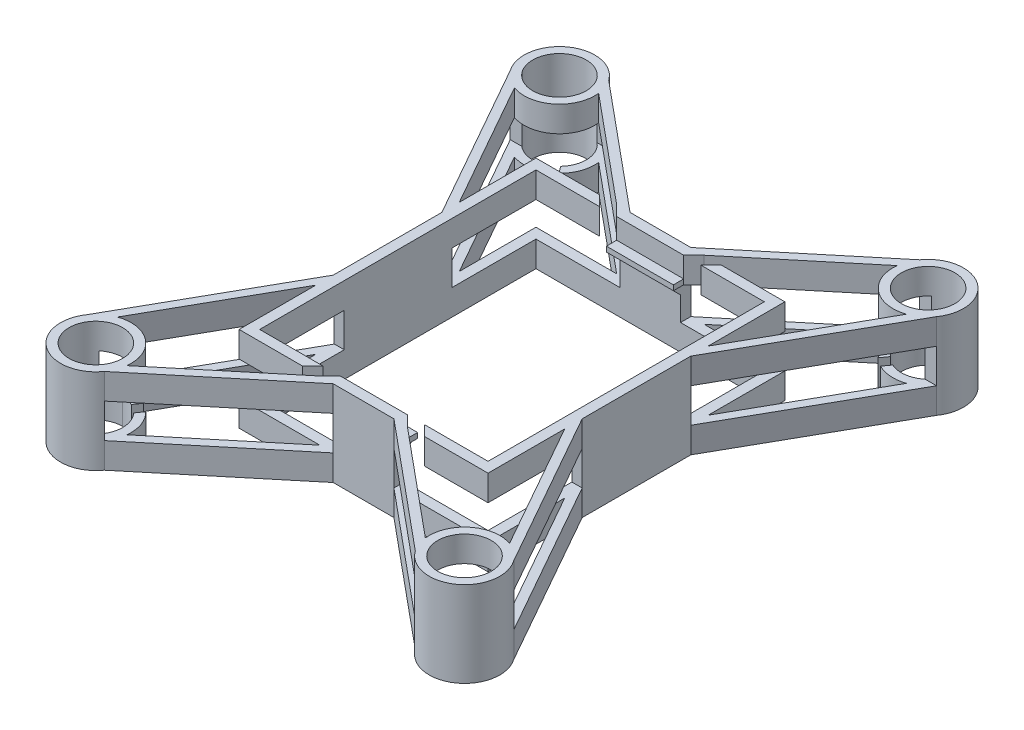
SolidWorks part; units mm, degrees
ref_plane "Front Plane" through (0, 0, 0) normal (0, 0, 1) x (1, 0, 0)
ref_plane "Top Plane" through (0, 0, 0) normal (0, 1, 0) x (1, 0, 0)
ref_plane "Right Plane" through (0, 0, 0) normal (1, 0, 0) x (0, 0, -1)
sketch "Sketch2" plane through (0, 0, 0) normal (0, 1, 0) x (1, 0, 0)
  line L0 (-24.0396, 23.0747) -> (-14.6061, 23.0747)
  line L1 (-22.8396, 21.8747) -> (3.8604, 21.8747)
  line L2 (-22.8396, 21.8747) -> (-22.8396, -10.4253)
  line L3 (-22.8396, -10.4253) -> (3.8604, -10.4253)
  line L4 (3.8604, 21.8747) -> (3.8604, -10.4253)
  line L5 (5.0604, 23.0747) -> (5.0604, 14.1087)
  line L6 (-24.0396, -11.6253) -> (-14.6061, -11.6253)
  line L7 (-24.0396, 23.0747) -> (-24.0396, 14.1087)
  line L8 (-32.4061, 28.9285) -> (-24.0396, 14.1087)
  line L9 (-26.9395, 33.3027) -> (-14.6061, 23.0747)
  line L10 (-34.4055, 30.4359) -> (-24.0396, 12.0747)
  line L11 (-27.6714, 35.2089) -> (-13.0396, 23.0747)
  line L12 (-33.5347, 30.9275) -> (-23.1688, 12.5663) construction
  line L13 (-28.3098, 34.4391) -> (-13.6779, 22.3049) construction
  line L14 (-24.0396, 12.0747) -> (-24.0396, -0.6253)
  line L15 (-24.0396, 23.0747) -> (-24.0396, -11.6253) construction
  line L16 (-13.0396, 23.0747) -> (-5.9396, 23.0747)
  line L17 (-24.0396, 23.0747) -> (5.0604, 23.0747) construction
  line L18 (-9.4896, 43.1002) -> (-9.4896, -24.274) construction
  line L19 (-35.8782, 5.7247) -> (17.7365, 5.7247) construction
  line L20 (8.6923, 35.2089) -> (-5.9396, 23.0747)
  line L21 (7.9603, 33.3027) -> (-4.373, 23.0747)
  line L22 (15.4263, 30.4359) -> (5.0604, 12.0747)
  line L23 (13.427, 28.9285) -> (5.0604, 14.1087)
  line L24 (-27.6714, -23.7596) -> (-13.0396, -11.6253)
  line L25 (-26.9395, -21.8534) -> (-14.6061, -11.6253)
  line L26 (-34.4055, -18.9866) -> (-24.0396, -0.6253)
  line L27 (-32.4061, -17.4792) -> (-24.0396, -2.6594)
  line L28 (8.6923, -23.7596) -> (-5.9396, -11.6253)
  line L29 (7.9603, -21.8534) -> (-4.373, -11.6253)
  line L30 (13.427, -17.4792) -> (5.0604, -2.6594)
  line L31 (15.4263, -18.9866) -> (5.0604, -0.6253)
  line L32 (-4.373, 23.0747) -> (5.0604, 23.0747)
  line L33 (5.0604, 12.0747) -> (5.0604, -0.6253)
  line L34 (5.0604, 23.0747) -> (5.0604, -11.6253) construction
  line L35 (5.0604, -2.6594) -> (5.0604, -11.6253)
  line L36 (-4.373, -11.6253) -> (5.0604, -11.6253)
  line L37 (-24.0396, -11.6253) -> (5.0604, -11.6253) construction
  line L38 (-13.0396, -11.6253) -> (-5.9396, -11.6253)
  line L39 (-24.0396, -2.6594) -> (-24.0396, -11.6253)
  circle A0 centre (-31.0384, 32.8223) radius 3.127
  arc A1 (-27.6714, 35.2089) -> (-34.4055, 30.4359) centre (-31.0384, 32.8223) ccw
  circle A2 centre (-31.0384, 32.8223) radius 4.127 construction
  arc A3 (-32.4061, 28.9285) -> (-26.9395, 33.3027) centre (-31.0384, 32.8223) ccw
  arc A4 (13.427, 28.9285) -> (7.9603, 33.3027) centre (12.0592, 32.8223) cw
  arc A5 (8.6923, 35.2089) -> (15.4263, 30.4359) centre (12.0592, 32.8223) cw
  circle A6 centre (12.0592, 32.8223) radius 3.127
  arc A7 (-32.4061, -17.4792) -> (-26.9395, -21.8534) centre (-31.0384, -21.373) cw
  arc A8 (-27.6714, -23.7596) -> (-34.4055, -18.9866) centre (-31.0384, -21.373) cw
  circle A9 centre (-31.0384, -21.373) radius 3.127
  circle A10 centre (12.0592, -21.373) radius 3.127
  arc A11 (8.6923, -23.7596) -> (15.4263, -18.9866) centre (12.0592, -21.373) ccw
  arc A12 (13.427, -17.4792) -> (7.9603, -21.8534) centre (12.0592, -21.373) ccw
  point P8 (-13.0396, 23.0747)
  point P9 (-24.0396, 12.0747)
  point P17 (-31.0384, 32.8223)
  point P42 (12.0592, 32.8223)
  point P54 (-31.0384, -21.373)
  point P65 (12.0592, -21.373)
  dimension "D6" = 6.254
  dimension "D11" = 6.254
  dimension "D1" = 26.7
  dimension "D2" = 32.3
  dimension "D4" = 11
  dimension "D5" = 11
  dimension "D8" = 1
  dimension "D9" = 1
  dimension "D10" = 12
  dimension "D3" = 1.2
  dimension "D7" = 1
extrude "Boss-Extrude1" add sketch "Sketch2" along normal blind 10
sketch "Sketch4" plane through (0, 0, 0) normal (1, 0, 0) x (0, 0, -1)
  line L1 (-18.9866, 10) -> (-18.9866, 0) construction
  line L2 (30.4359, 10) -> (30.4359, 0) construction
  line L5 (-18.9866, 5) -> (-18.9866, 7)
  line L6 (-18.9866, 7) -> (30.4359, 7)
  line L7 (30.4359, 5) -> (30.4359, 7)
  line L9 (-18.9866, 5) -> (-18.9866, 3)
  line L10 (-18.9866, 3) -> (30.4359, 3)
  line L11 (30.4359, 5) -> (30.4359, 3)
  dimension "D1" = 2
  dimension "D2" = 2
extrude "Cut-Extrude1" cut sketch "Sketch4" against normal through all both and the other way through all
sketch "Sketch5" plane through (0, 0, 0) normal (0, 0, 1) x (1, 0, 0)
  line L1 (-27.6714, 10) -> (-27.6714, 0) construction
  line L2 (8.6923, 10) -> (8.6923, 0) construction
  line L5 (-27.6714, 5) -> (-27.6714, 7)
  line L6 (-27.6714, 7) -> (8.6923, 7)
  line L7 (8.6923, 5) -> (8.6923, 7)
  line L9 (8.6923, 5) -> (8.6923, 3)
  line L10 (8.6923, 3) -> (-27.6714, 3)
  line L11 (-27.6714, 5) -> (-27.6714, 3)
extrude "Cut-Extrude2" cut sketch "Sketch5" against normal through all both and the other way through all
sketch "Sketch6" plane through (-27.6714, 0, 0) normal (1, 0, 0) x (0, 0, -1)
  line L0 (30.4359, 3) -> (30.4359, 7) construction
  line L1 (30.4359, 7) -> (35.2089, 7)
  line L2 (30.4359, 7) -> (30.4359, 3)
  line L3 (30.4359, 3) -> (35.2089, 3)
  line L4 (35.2089, 7) -> (35.2089, 3)
  line L5 (35.2089, 7) -> (30.4359, 7) construction
extrude "Cut-Extrude3" cut sketch "Sketch6" against normal up to surface (1.3465 mm away) up to face at (-31.0384, 5, -30.0656)
sketch "Sketch7" plane through (-27.6714, 0, 0) normal (1, 0, 0) x (0, 0, -1)
  line L1 (-23.7596, 7) -> (-18.9866, 7)
  line L2 (-23.7596, 7) -> (-23.7596, 3)
  line L3 (-23.7596, 3) -> (-18.9866, 3)
  line L4 (-18.9866, 7) -> (-18.9866, 3)
extrude "Cut-Extrude4" cut sketch "Sketch7" against normal up to surface (1.3462 mm away) up to face at (-31.0384, 5, 18.6163)
sketch "Sketch8" plane through (8.6923, 0, 0) normal (-1, 0, 0) x (0, 0, 1)
  line L0 (-35.2089, 3) -> (-30.4359, 3) construction
  line L1 (-35.2089, 7) -> (-30.4359, 7)
  line L2 (-35.2089, 7) -> (-35.2089, 3)
  line L3 (-35.2089, 3) -> (-30.4359, 3)
  line L4 (-30.4359, 7) -> (-30.4359, 3)
  line L5 (-30.4359, 7) -> (-30.4359, 3) construction
extrude "Cut-Extrude5" cut sketch "Sketch8" against normal up to surface (1.3462 mm away) up to face at (12.0592, 5, -30.0656)
sketch "Sketch9" plane through (8.6923, 0, 0) normal (-1, 0, 0) x (0, 0, 1)
  line L1 (18.9866, 7) -> (23.7596, 7)
  line L2 (18.9866, 7) -> (18.9866, 3)
  line L3 (18.9866, 3) -> (23.7596, 3)
  line L4 (23.7596, 7) -> (23.7596, 3)
extrude "Cut-Extrude6" cut sketch "Sketch9" against normal up to surface (1.3465 mm away) up to face at (12.0592, 5, 18.6163)
sketch "Sketch10" plane through (0, 3, 0) normal (0, 1, 0) x (1, 0, 0)
  line L0 (-22.8396, 21.8747) -> (-22.8396, -10.4253) construction
  line L1 (-24.0396, 12.0747) -> (-22.8396, 12.0747)
  line L2 (-24.0396, 12.0747) -> (-24.0396, -0.536)
  line L3 (-24.0396, -0.536) -> (-22.8396, -0.536)
  line L4 (-22.8396, 12.0747) -> (-22.8396, -0.536)
  line L5 (3.8604, 21.8747) -> (-22.8396, 21.8747) construction
  line L6 (-13.0396, 23.0747) -> (-5.9396, 23.0747)
  line L7 (-13.0396, 23.0747) -> (-13.0396, 21.8747)
  line L8 (-13.0396, 21.8747) -> (-5.9396, 21.8747)
  line L9 (-5.9396, 23.0747) -> (-5.9396, 21.8747)
  line L10 (-22.8396, -10.4253) -> (3.8604, -10.4253) construction
  line L15 (3.8604, -10.4253) -> (3.8604, 21.8747) construction
  line L16 (5.0604, 12.0747) -> (3.8604, 12.0747)
  line L17 (5.0604, 12.0747) -> (5.0604, -0.6253)
  line L18 (5.0604, -0.6253) -> (3.8604, -0.6253)
  line L19 (3.8604, 12.0747) -> (3.8604, -0.6253)
  line L20 (-13.0396, -11.6253) -> (-5.9396, -11.6253)
  line L21 (-13.0396, -11.6253) -> (-13.0396, -10.4253)
  line L22 (-13.0396, -10.4253) -> (-5.9396, -10.4253)
  line L23 (-5.9396, -11.6253) -> (-5.9396, -10.4253)
extrude "Boss-Extrude2" add sketch "Sketch10" along normal up to surface (4 mm away) up to face at (-9.4896, 7, -5.7247)
sketch "Sketch11" plane through (0, 0, 0) normal (0, -1, 0) x (1, 0, 0)
  line L0 (-24.0396, 11.6253) -> (-31.0384, 21.373) construction
  line L1 (-29.0577, 19.6641) -> (-30.0523, 18.9499)
  line L2 (-30.0523, 18.9499) -> (-28.7834, 17.1827)
  line L3 (-28.7834, 17.1827) -> (-27.7888, 17.8968)
  line L4 (-27.7888, 17.8968) -> (-29.0577, 19.6641)
  line L5 (-9.4896, 17.1827) -> (-9.4896, -28.9277) construction
  line L6 (-86.1455, -5.7247) -> (24.0687, -5.7247)
  line L7 (9.8043, 17.1827) -> (8.8097, 17.8968)
  line L8 (11.0732, 18.9499) -> (9.8043, 17.1827)
  line L9 (10.0786, 19.6641) -> (11.0732, 18.9499)
  line L10 (8.8097, 17.8968) -> (10.0786, 19.6641)
  line L11 (-28.7834, -28.632) -> (-27.7888, -29.3461)
  line L12 (-30.0523, -30.3992) -> (-28.7834, -28.632)
  line L13 (-29.0577, -31.1134) -> (-30.0523, -30.3992)
  line L14 (-27.7888, -29.3461) -> (-29.0577, -31.1134)
  line L15 (11.0732, -30.3992) -> (9.8043, -28.632)
  line L16 (10.0786, -31.1134) -> (11.0732, -30.3992)
  line L17 (8.8097, -29.3461) -> (10.0786, -31.1134)
  line L18 (9.8043, -28.632) -> (8.8097, -29.3461)
  point P7 (-29.555, 19.307)
  point P14 (-31.0384, -5.7247)
  circle M12 centre (-31.0384, 21.373) radius 3.127
  circle M13 centre (-31.0384, -32.8223) radius 3.127
  arc M38 (-26.9395, -33.3027) -> (-32.4061, -28.9285) centre (-31.0384, -32.8223) ccw
  arc M43 (13.427, -28.9285) -> (7.9603, -33.3027) centre (12.0592, -32.8223) ccw
  arc M52 (-32.4061, 17.4792) -> (-26.9395, 21.8534) centre (-31.0384, 21.373) ccw
  circle M54 centre (12.0592, -32.8223) radius 3.127
  dimension "D1" = 90
extrude "Cut-Extrude7" cut sketch "Sketch11" against normal up to surface (3 mm away) contours L17 L15 M43 M54 | L14 L12 M38 M13 | L4 L2 M52 M12 | L8 L7 L10 L9 region at (-28.9333, 0, 18.4411) region at (-28.9333, 0, -29.8905) region at (9.9542, 0, -29.8905) up to face at (5.1845, 3, 12.7454)
sketch "Sketch12" plane through (0, 10, 0) normal (0, 1, 0) x (1, 0, 0)
  line L0 (-14.6061, 23.0747) -> (-13.4061, 21.8747)
  line L1 (3.8604, 21.8747) -> (-22.8396, 21.8747) construction
  line L2 (-13.4061, 21.8747) -> (-15.4061, 21.8747)
  line L3 (-15.4061, 21.8747) -> (-16.6061, 23.0747)
  line L4 (-24.0396, 23.0747) -> (-14.6061, 23.0747) construction
  line L5 (-16.6061, 23.0747) -> (-14.6061, 23.0747)
  line L6 (-9.4896, 27.4573) -> (-9.4896, -27.6431) construction
  line L7 (-43.1537, 5.7247) -> (27.6634, 5.7247) construction
  line L8 (-3.573, 21.8747) -> (-2.373, 23.0747)
  line L9 (-5.573, 21.8747) -> (-3.573, 21.8747)
  line L10 (-4.373, 23.0747) -> (-5.573, 21.8747)
  line L11 (-2.373, 23.0747) -> (-4.373, 23.0747)
  line L12 (-15.4061, -10.4253) -> (-16.6061, -11.6253)
  line L13 (-13.4061, -10.4253) -> (-15.4061, -10.4253)
  line L14 (-14.6061, -11.6253) -> (-13.4061, -10.4253)
  line L15 (-16.6061, -11.6253) -> (-14.6061, -11.6253)
  line L16 (-5.573, -10.4253) -> (-3.573, -10.4253)
  line L17 (-4.373, -11.6253) -> (-5.573, -10.4253)
  line L18 (-2.373, -11.6253) -> (-4.373, -11.6253)
  line L19 (-3.573, -10.4253) -> (-2.373, -11.6253)
  dimension "D1" = 2
extrude "Cut-Extrude9" cut sketch "Sketch12" against normal up to surface (3 mm away) up to face at (-24.1636, 7, 12.7454)
sketch "Sketch13" plane through (0, 0, -21.8747) normal (0, 0, 1) x (1, 0, 0)
  line L0 (-5.573, 7) -> (-5.573, 10) construction
  line L1 (-13.4061, 7) -> (-5.573, 7)
  line L2 (-13.4061, 7) -> (-13.4061, 7.6)
  line L3 (-13.4061, 7.6) -> (-5.573, 7.6)
  line L4 (-5.573, 7) -> (-5.573, 7.6)
  dimension "D1" = 0.6
extrude "Boss-Extrude3" add sketch "Sketch13" along normal blind 1.2
chamfer "Chamfer1" distance 1.2 angle 45 1 edges at (-9.4896, 7, -21.8747)
sketch "Sketch14" plane through (0, 0, 10.4253) normal (0, 0, -1) x (-1, 0, 0)
  line L0 (13.4061, 7) -> (13.4061, 10) construction
  line L1 (5.573, 7) -> (13.4061, 7)
  line L2 (5.573, 7) -> (5.573, 7.6)
  line L3 (5.573, 7.6) -> (13.4061, 7.6)
  line L4 (13.4061, 7) -> (13.4061, 7.6)
  dimension "D1" = 0.6
extrude "Boss-Extrude4" add sketch "Sketch14" along normal blind 1.2
chamfer "Chamfer2" distance 1.2 angle 45 1 edges at (-9.4896, 7, 10.4253)
